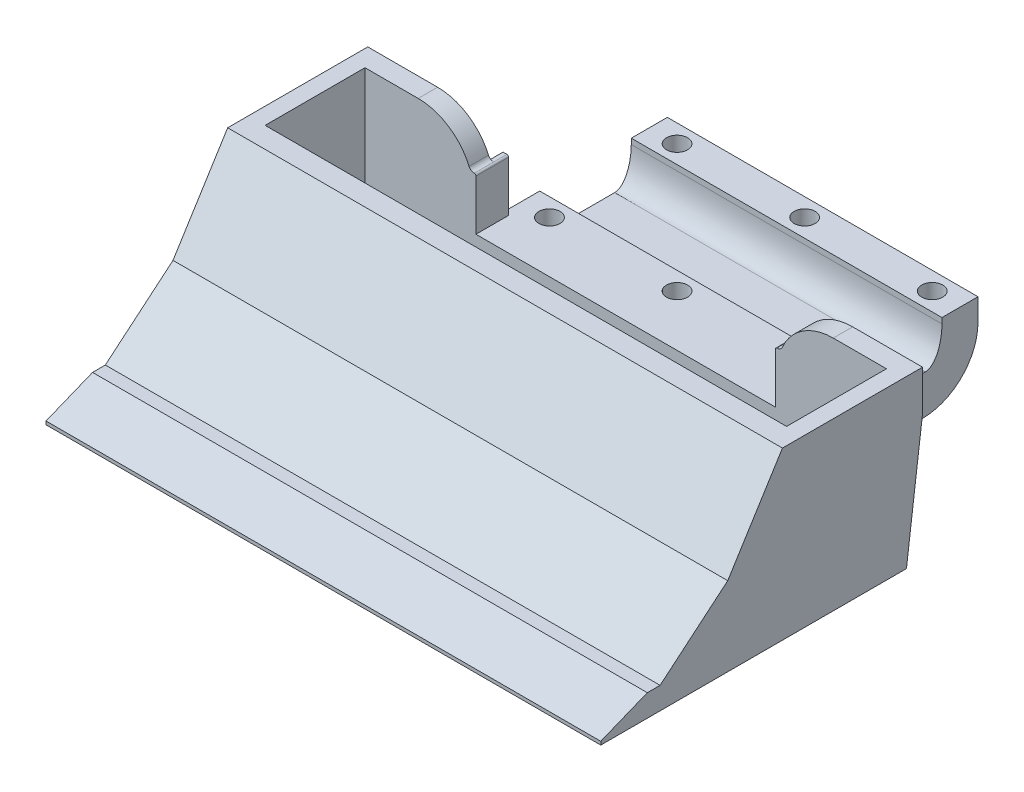
SolidWorks part; units mm, degrees
ref_plane "Plano frontal" through (0, 0, 0) normal (0, 0, 1) x (1, 0, 0)
ref_plane "Plano superior" through (0, 0, 0) normal (0, 1, 0) x (1, 0, 0)
ref_plane "Plano direito" through (0, 0, 0) normal (1, 0, 0) x (0, 0, -1)
sketch "Esboço2" plane through (0, 0, 0) normal (0, 1, 0) x (1, 0, 0)
  line L0 (0, 0) -> (0, 58)
  line L1 (0, 58) -> (22, 58)
  line L2 (22, 58) -> (22, 90)
  line L3 (22, 90) -> (78, 90)
  line L4 (78, 90) -> (78, 58)
  line L5 (78, 58) -> (100, 58)
  line L6 (100, 58) -> (100, 0)
  line L7 (100, 0) -> (0, 0)
  dimension "D1" = 100
  dimension "D2" = 56
  dimension "D3" = 90
  dimension "D5" = 32
extrude "Ressalto-extrusão1" add sketch "Esboço2" along normal blind 30
sketch "Esboço3" plane through (100, 0, 0) normal (1, 0, 0) x (0, 0, -1)
  line L0 (0, 0.6) -> (9.8284, 4.5709)
  line L1 (0, 30) -> (0, 0) construction
  line L2 (9.8284, 4.5709) -> (22.1268, 14.8905)
  line L3 (22.1268, 14.8905) -> (31.5683, 30)
  line L4 (0, 30) -> (58, 30) construction
  line L5 (31.5683, 30) -> (0, 30)
  line L6 (0, 30) -> (0, 0.6)
  line L7 (0, 0) -> (58, 0) construction
  dimension "D1" = 0.6
  dimension "D2" = 22
  dimension "D3" = 40
  dimension "D4" = 18
  dimension "D5" = 15.1095
  dimension "D6" = 12.2984
extrude "Corte-extrusão1" cut sketch "Esboço3" against normal blind 100
sketch "Esboço4" plane through (0, 0, 0) normal (0, -1, 0) x (1, 0, 0)
  line L0 (0, -58) -> (0, 0) construction
  line L1 (3, -53) -> (97, -53)
  line L2 (3, -53) -> (3, -28)
  line L3 (3, -28) -> (97, -28)
  line L4 (97, -53) -> (97, -28)
  line L5 (22, -58) -> (0, -58) construction
  dimension "D1" = 25
  dimension "D2" = 94
  dimension "D3" = 3
  dimension "D4" = 5
extrude "Corte-extrusão2" cut sketch "Esboço4" against normal blind 10
sketch "Esboço5" plane through (0, 30, 0) normal (0, 1, 0) x (1, 0, 0)
  line L0 (0, 58) -> (0, 31.5683) construction
  line L1 (3, 54.5) -> (97, 54.5)
  line L2 (3, 54.5) -> (3, 36.5)
  line L3 (3, 36.5) -> (97, 36.5)
  line L4 (97, 54.5) -> (97, 36.5)
  line L6 (100, 31.5683) -> (100, 58) construction
  line L7 (22, 58) -> (0, 58) construction
  dimension "D1" = 3
  dimension "D2" = 3
  dimension "D3" = 3.5
  dimension "D4" = 18
extrude "Corte-extrusão3" cut sketch "Esboço5" against normal blind 20 contours L2 L1 L4 L3
sketch "Esboço7" plane through (100, 0, 0) normal (1, 0, 0) x (0, 0, -1)
  line L0 (28, 10) -> (36.5, 30)
  line L1 (36.5, 30) -> (36.5, 10)
  line L2 (36.5, 10) -> (28, 10)
extrude "Corte-extrusão7" cut sketch "Esboço7" against normal up to surface (97 mm away) from surface up to face at (3, 12.5, -43) starting at face at (97, 12.5, -43)
sketch "Esboço8" plane through (78, 0, 0) normal (1, 0, 0) x (0, 0, -1)
  line L0 (90, 30) -> (90, 0) construction
  line L1 (58, 30) -> (90, 30)
  line L2 (58, 30) -> (58, 15)
  line L3 (58, 15) -> (90, 15)
  line L4 (90, 30) -> (90, 15)
  line L5 (58, 0) -> (90, 0) construction
  dimension "D1" = 15
extrude "Corte-extrusão8" cut sketch "Esboço8" against normal blind 56
sketch "Esboço9" plane through (78, 0, 0) normal (1, 0, 0) x (0, 0, -1)
  line L0 (67, 15) -> (67, 7)
  line L1 (58, 15) -> (90, 15) construction
  line L2 (67, 7) -> (83.5, 7)
  line L3 (83.5, 7) -> (83.5, 15)
  line L4 (83.5, 15) -> (67, 15)
  line L5 (90, 15) -> (90, 0) construction
  dimension "D1" = 16.5
  dimension "D2" = 8
  dimension "D3" = 6.5
extrude "Corte-extrusão9" cut sketch "Esboço9" against normal blind 56
fillet "Filete1" radius 6 1 edges at (50, 7, -67) second distance 3 first distance on face at (50, 11, -67)
fillet "Filete2" radius 3 1 edges at (50, 7, -83.5) second distance 6 first distance on face at (43, 7, -73.375)
fillet "Filete3" radius 10 1 edges at (50, 0, -90)
sketch "Esboço12" plane through (22, 0, 0) normal (-1, 0, 0) x (0, 0, 1)
  line L0 (-90, 15) -> (-58, 15)
  line L1 (-58, 15) -> (-58, 14)
  line L2 (-58, 15) -> (-58, 0) construction
  line L3 (-58, 14) -> (-90, 14)
  line L4 (-90, 15) -> (-90, 10) construction
  line L5 (-90, 14) -> (-90, 15)
  dimension "D1" = 1
extrude "Corte-extrusão12" cut sketch "Esboço12" against normal blind 68
sketch "Esboço14" plane through (0, 0, -58) normal (0, 0, -1) x (-1, 0, 0)
  line L0 (-78, 14) -> (-22, 14)
  line L1 (-22, 14) -> (-22, 30)
  line L2 (-100, 30) -> (0, 30) construction
  line L3 (-22, 30) -> (-78, 30)
  line L4 (-78, 30) -> (-78, 14)
extrude "Corte-extrusão13" cut sketch "Esboço14" against normal up to next
sketch "Esboço15" plane through (100, 0, 0) normal (1, 0, 0) x (0, 0, -1)
  line L12 (9.049, 4.256) -> (10.049, 4.256)
  line L13 (0, 0.6) -> (9.8284, 4.5709) construction
  line L14 (10.049, 4.256) -> (10.049, 4.756)
  line L15 (9.8284, 4.5709) -> (22.1268, 14.8905) construction
  line L16 (10.049, 4.756) -> (9.049, 4.256)
  dimension "D1" = 1
  dimension "D2" = 0.5
extrude "Corte-extrusão14" cut sketch "Esboço15" against normal through all
sketch "Esboço16" plane through (0, 14, 0) normal (0, 1, 0) x (1, 0, 0)
  line L0 (78, 90) -> (22, 90) construction
  line L1 (78, 90) -> (78, 83.5) construction
  line L2 (22, 90) -> (22, 83.5) construction
  line L3 (22, 75.25) -> (78, 75.25) construction
  line L4 (78, 70) -> (78, 80.5) construction
  line L5 (22, 70) -> (22, 80.5) construction
  line L6 (22, 90) -> (47, 90) construction
  line L7 (78, 90) -> (53, 90) construction
  circle A1 centre (73, 86.75) radius 1.9
  circle A2 centre (27, 86.75) radius 1.9
  circle A3 centre (73, 63.75) radius 1.9
  circle A5 centre (27, 63.75) radius 1.9
  circle A10 centre (50, 86.75) radius 1.9
  circle A11 centre (50, 63.75) radius 1.9
  point P8 (0, 0)
  point P11 (78, 86.75)
  point P16 (50, 90)
  point P17 (0, 0)
  dimension "D1" = 3.8
  dimension "D2" = 3.8
  dimension "D3" = 3.8
  dimension "D4" = 5
  dimension "D5" = 5
  dimension "D7" = 25
  dimension "D8" = 25
extrude "Corte-extrusão15" cut sketch "Esboço16" against normal through all
sketch "Esboço19" plane through (78, 0, 0) normal (-1, 0, 0) x (0, 0, 1)
  line L1 (-54.5, 14) -> (-60.39, 14)
  line L2 (-54.5, 14) -> (-54.5, 23.3795)
  line L3 (-54.5, 23.3795) -> (-60.39, 23.3795)
  line L4 (-60.39, 14) -> (-60.39, 23.3795)
extrude "Ressalto-extrusão4" add sketch "Esboço19" along normal blind 1
sketch "Esboço20" plane through (22, 0, 0) normal (1, 0, 0) x (0, 0, -1)
  line L1 (54.5, 14) -> (60.39, 14)
  line L2 (54.5, 14) -> (54.5, 23.3795)
  line L3 (54.5, 23.3795) -> (60.39, 23.3795)
  line L4 (60.39, 14) -> (60.39, 23.3795)
extrude "Ressalto-extrusão5" add sketch "Esboço20" along normal blind 1
fillet "Filete5" radius 10 2 edges at (22, 30, -56.25) (78, 30, -56.25)
fillet "Filete6" radius 0.3 2 edges at (77, 23.3795, -57.445) (23, 23.3795, -57.445)
fillet "Filete7" radius 1 2 edges at (22, 23.3795, -56.25) (78, 23.3795, -56.25)
sketch "Esboço22" plane through (0, 0, 0) normal (-1, 0, 0) x (0, 0, 1)
  line L5 (-58, 0) -> (-58, 22.7053)
  line L6 (-58, 23.3795) -> (-58, 0) construction
  line L7 (-58, 22.7053) -> (-55.1054, 0)
  line L8 (-58, 0) -> (0, 0) construction
  line L9 (-55.1054, 0) -> (-58, 0)
  dimension "D1" = 22.7053
  dimension "D2" = 277.265
extrude "Corte-extrusão17" cut sketch "Esboço22" against normal up to surface (22 mm away) up to face at (22, 11.5914, -72.4693)
sketch "Esboço23" plane through (100, 0, 0) normal (1, 0, 0) x (0, 0, -1)
  line L0 (58, 0) -> (55.1029, 0)
  line L1 (0, 0) -> (58, 0) construction
  line L2 (55.1029, 0) -> (58, 22.71)
  line L3 (58, 30) -> (58, 0) construction
  line L4 (58, 22.71) -> (58, 0)
  dimension "D1" = 22.71
  dimension "D2" = 277.27
extrude "Corte-extrusão18" cut sketch "Esboço23" against normal up to surface (22 mm away) up to face at (78, 11.5914, -72.9309)
sketch "Esboço27" plane through (0, 0, 0) normal (-1, 0, 0) x (0, 0, 1)
  line L0 (-31.5683, 30) -> (-22.1268, 14.8905)
  line L1 (-22.1268, 14.8905) -> (-10.049, 4.756)
  line L3 (-10.6918, 3.99) -> (-22.8909, 14.2263)
  line L4 (-22.8909, 14.2263) -> (-32.7474, 30)
  line L5 (-58, 30) -> (-31.5683, 30) construction
  line L6 (-32.7474, 30) -> (-31.5683, 30)
  line L7 (-10.6918, 3.99) -> (-7.995, 3.99)
  line L8 (-7.995, 3.99) -> (-10.049, 4.756)
  dimension "D1" = 1
  dimension "D2" = 1
extrude "Corte-extrusão19" cut sketch "Esboço27" against normal blind 124
